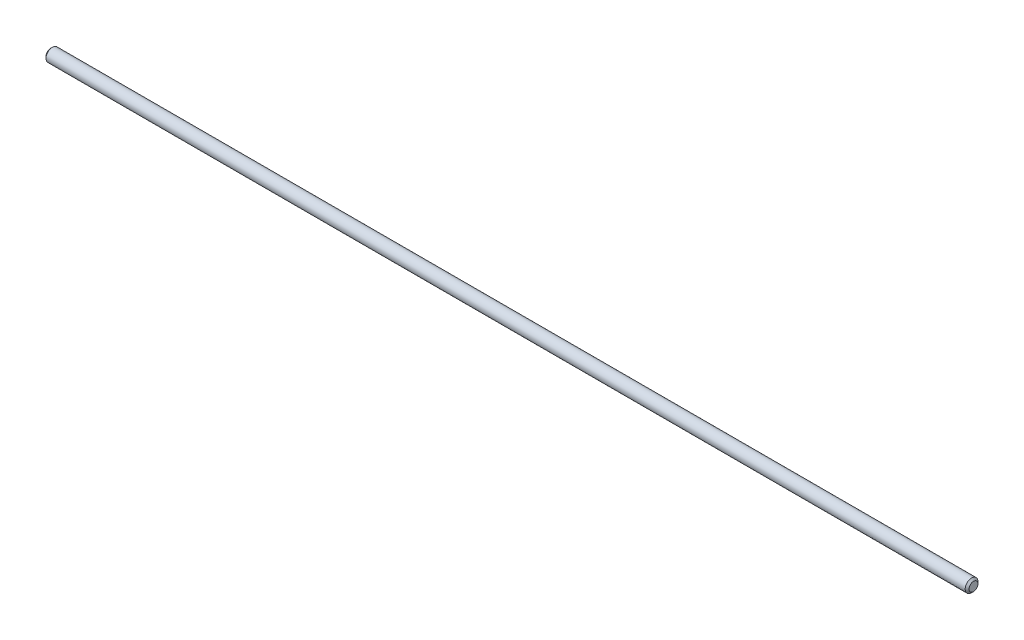
SolidWorks part; units mm, degrees
ref_plane "Front Plane" through (0, 0, 0) normal (0, 0, 1) x (1, 0, 0)
ref_plane "Top Plane" through (0, 0, 0) normal (0, 1, 0) x (1, 0, 0)
ref_plane "Right Plane" through (0, 0, 0) normal (1, 0, 0) x (0, 0, -1)
sketch "Sketch1" plane through (0, 0, 0) normal (0, 0, 1) x (1, 0, 0)
  line L0 (-228.6, 0) -> (228.6, 0) construction
  line L1 (228.6, 3.175) -> (228.6, -3.175) construction
  line L2 (-228.6, 3.175) -> (-228.6, -3.175) construction
  point P6 (224.155, -3.175)
  dimension "Thread Diameter" = 6.35
  dimension "Length" = 457.2
  dimension "D1" = 4.445
sketch "Sketch2" plane through (0, 0, 0) normal (1, 0, 0) x (0, 0, -1)
  circle A0 centre (0, 0) radius 3.175
extrude "Boss-Extrude1" add sketch "Sketch2" against normal up to vertex (228.6 mm away) and the other way up to vertex (228.6 mm away) up to point (-228.6, 0, 0) other way up to point (228.6, 0, 0)
cosmetic thread "Cosmetic Thread1" parameters "D2"=4.8387
sketch "Sketch3" plane through (228.6, 0, 0) normal (1, 0, 0) x (0, 0, -1)
  circle A1 centre (0, 0) radius 3.175
  circle A2 centre (0, 0) radius 3.175
  dimension "D1" = 0
curve "Helix/Spiral1" pitch 1.27 height 458.47 turns 361 parameters "Pitch"=1.27
chamfer "Chamfer1" distance 0.9525 angle 45 2 edges at (-228.6, 0, -3.175) (228.6, 0, -3.175)
sketch "Sketch4" plane through (0, 0, 0) normal (0, 0, 1) x (1, 0, 0)
  line L0 (228.5206, 3.3125) -> (229.1556, 2.2126) construction
  line L1 (229.1556, 2.2126) -> (229.7906, 3.3125) construction
  line L2 (229.7906, 3.3125) -> (228.5206, 3.3125) construction
  line L3 (229.1556, 3.3125) -> (229.1556, 3.175) construction
  line L4 (229.1556, 2.2126) -> (229.1556, 2.3501) construction
  line L5 (229.0763, 2.3501) -> (229.235, 2.3501) construction
  line L6 (228.6, 3.175) -> (229.7113, 3.175) construction
  line L7 (229.0763, 2.3501) -> (228.5603, 3.2437)
  line L8 (229.0763, 2.3501) -> (229.235, 2.3501)
  line L9 (228.5603, 3.2437) -> (229.7509, 3.2437)
  line L10 (229.7509, 3.2437) -> (229.235, 2.3501)
  point P13 (229.1556, 3.2437)
  dimension "D2" = 0.1588
sweep "Cut-Sweep3" [suppressed] cut profiles "Sketch4" path "Helix/Spiral1"
equation "\"D3@Helix/Spiral1\" = \"Length@Sketch1\"+\"Pitch@Helix/Spiral1\""
equation "\"D1@Chamfer1\" = \"Pitch@Helix/Spiral1\"*.75"
equation "\"D1@Sketch4\" = \"Pitch@Helix/Spiral1\""
equation "\"D2@Sketch4\" = \"D1@Sketch4\"/8"
equation "\"D1@Sketch1\" = \"Pitch@Helix/Spiral1\"*3.50"
